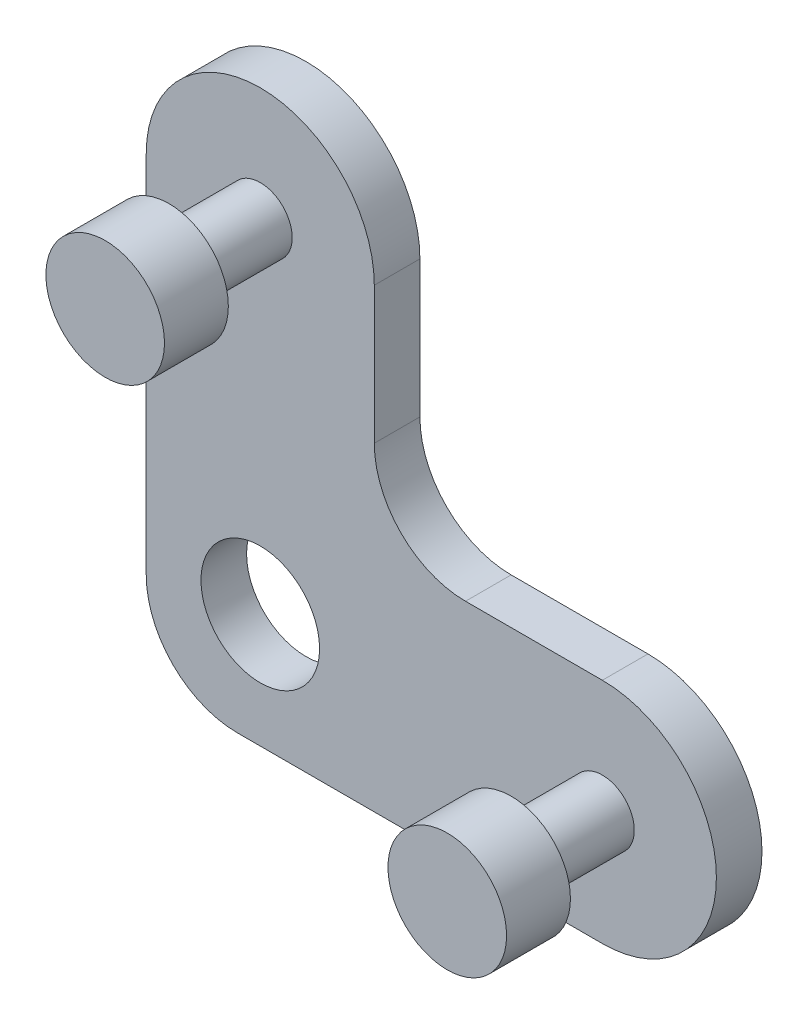
SolidWorks part; units mm, degrees
ref_plane "Front Plane" through (0, 0, 0) normal (0, 0, 1) x (1, 0, 0)
ref_plane "Top Plane" through (0, 0, 0) normal (0, 1, 0) x (1, 0, 0)
ref_plane "Right Plane" through (0, 0, 0) normal (1, 0, 0) x (0, 0, -1)
sketch "Sketch1" plane through (0, 0, 0) normal (0, 0, 1) x (1, 0, 0)
  line L0 (0, 12.7) -> (0, 2.54)
  line L1 (2.54, 0) -> (12.7, 0)
  line L2 (6.35, 12.7) -> (6.35, 8.89)
  line L3 (8.89, 6.35) -> (12.7, 6.35)
  line L4 (0, 12.7) -> (0, 0) construction
  line L5 (0, 0) -> (12.7, 0) construction
  line L6 (6.35, 12.7) -> (6.35, 6.35) construction
  line L7 (6.35, 6.35) -> (12.7, 6.35) construction
  arc A0 (0, 12.7) -> (6.35, 12.7) centre (3.175, 12.7) cw
  arc A1 (12.7, 0) -> (12.7, 6.35) centre (12.7, 3.175) ccw
  arc A2 (0, 2.54) -> (2.54, 0) centre (2.54, 2.54) ccw
  arc A3 (6.35, 8.89) -> (8.89, 6.35) centre (8.89, 8.89) ccw
  point P12 (0, 0)
  dimension "D4" = 2.54
  dimension "D1" = 12.7
  dimension "D2" = 12.7
  dimension "D3" = 6.35
extrude "body" add sketch "Sketch1" along normal blind 1.27
sketch "Sketch2" plane through (0, 0, 1.27) normal (0, 0, 1) x (1, 0, 0)
  circle A0 centre (3.175, 12.7) radius 0.889
  circle A1 centre (12.7, 3.175) radius 0.889
  dimension "D1" = 1.778
  dimension "D2" = 1.778
extrude "nubs" add sketch "Sketch2" along normal blind 2.54
sketch "Sketch3" plane through (0, 0, 3.81) normal (0, 0, 1) x (1, 0, 0)
  circle A0 centre (12.7, 3.175) radius 1.651
  circle A1 centre (3.175, 12.7) radius 1.651
  dimension "D1" = 3.302
  dimension "D2" = 3.302
extrude "don't let it fall off" add sketch "Sketch3" along normal blind 1.778
sketch "references" plane through (0, 0, 1.27) normal (0, 0, 1) x (1, 0, 0)
  line L0 (38.1, 3.175) -> (-5.5398, 3.175) construction
  line L1 (3.175, 38.1) -> (3.175, -6.489) construction
ref_point "centre of hole"
sketch "Sketch5" plane through (0, 0, 1.27) normal (0, 0, 1) x (1, 0, 0)
  circle A0 centre (3.175, 3.175) radius 1.651
  dimension "D1" = 3.302
extrude "attach to side" cut sketch "Sketch5" against normal up to next
